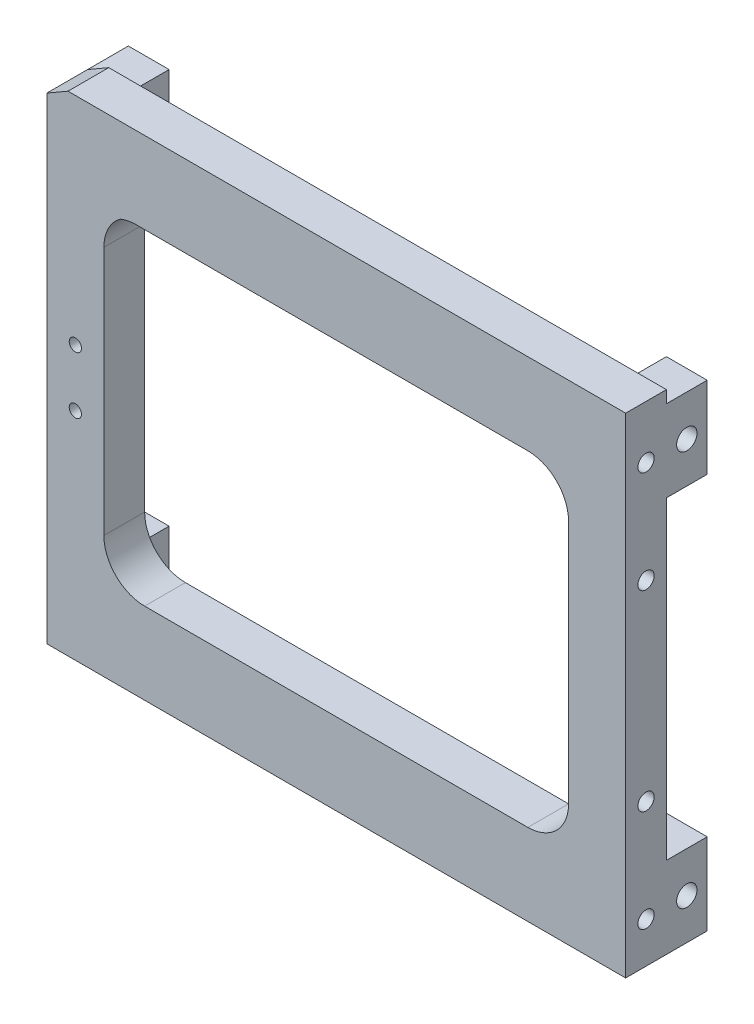
SolidWorks part; units mm, degrees
material "1060 合金"
ref_plane "前视基准面" through (0, 0, 0) normal (0, 0, 1) x (1, 0, 0)
ref_plane "上视基准面" through (0, 0, 0) normal (0, 1, 0) x (1, 0, 0)
ref_plane "右视基准面" through (0, 0, 0) normal (1, 0, 0) x (0, 0, -1)
sketch "草图1" plane through (0, 0, 0) normal (0, 0, 1) x (1, 0, 0)
  line L0 (-51.8038, 40) -> (-57, 37)
  line L1 (-65.8038, 60) -> (71, 60)
  line L2 (-71, 57) -> (-71, -60)
  line L3 (-71, -60) -> (71, -60)
  line L4 (71, 60) -> (71, -60)
  line L5 (-51.8038, 40) -> (57, 40)
  line L6 (-57, 37) -> (-57, -40)
  line L7 (-57, -40) -> (57, -40)
  line L8 (57, 40) -> (57, -40)
  line L9 (-65.8038, 60) -> (-71, 57)
  point P0 (0, -40)
  point P8 (71, 0)
  point P9 (57, 0)
  point P11 (2.5981, 60)
  point P12 (2.5981, 40)
  dimension "D1" = 142
  dimension "D2" = 117
  dimension "D3" = 20
  dimension "D4" = 14
  dimension "D5" = 60
  dimension "D6" = 14
  dimension "D7" = 3
extrude "凸台-拉伸1" add sketch "草图1" along normal mid plane 10
fillet "圆角1" radius 10 3 edges at (-57, -40, 0) (57, -40, 0) (57, 40, 0)
fillet "圆角2" radius 10 2 edges at (-51.8038, 40, 0) (-57, 37, 0)
sketch "草图2" plane through (0, 0, -5) normal (0, 0, 1) x (1, 0, 0)
  line L0 (71, -60) -> (71, 60) construction
  line L1 (-71, 57) -> (-61, 57)
  line L2 (-71, 57) -> (-71, 37)
  line L3 (-71, 37) -> (-61, 37)
  line L4 (-61, 57) -> (-61, 37)
  line L5 (-71, -60) -> (-61, -60)
  line L6 (-71, -60) -> (-71, -40)
  line L7 (-71, -40) -> (-61, -40)
  line L8 (-61, -60) -> (-61, -40)
  line L9 (71, 57) -> (61, 57)
  line L10 (71, 57) -> (71, 37)
  line L11 (71, 37) -> (61, 37)
  line L12 (61, 57) -> (61, 37)
  line L15 (71, -60) -> (61, -60)
  line L16 (71, -60) -> (71, -40)
  line L17 (71, -40) -> (61, -40)
  line L18 (61, -60) -> (61, -40)
  dimension "D1" = 20
  dimension "D2" = 20
  dimension "D3" = 10
  dimension "D4" = 10
extrude "凸台-拉伸2" add sketch "草图2" against normal blind 10
sketch "草图3" plane through (-71, 0, 0) normal (-1, 0, 0) x (0, 0, 1)
  line L0 (-15, 47) -> (5, 47) construction
  line L1 (-15, 57) -> (-15, 37) construction
  line L2 (5, 57) -> (5, -60) construction
  line L3 (-15, -50) -> (5, -50) construction
  line L4 (-15, -40) -> (-15, -60) construction
  circle A0 centre (-10, 47) radius 2.5
  circle A1 centre (0, 47) radius 2
  circle A2 centre (-10, -50) radius 2.5
  circle A3 centre (0, -50) radius 2
  circle A4 centre (0, 22) radius 2
  circle A5 centre (0, -25) radius 2
  dimension "D1" = 4
  dimension "D5" = 5
  dimension "D2" = 5
  dimension "D3" = 25
  dimension "D4" = 25
extrude "切除-拉伸1" cut sketch "草图3" against normal blind 12
sketch "草图4" plane through (71, 0, 0) normal (1, 0, 0) x (0, 0, -1)
  circle A0 centre (10, -50) radius 2.5 construction
  circle A1 centre (0, -50) radius 2 construction
  circle A2 centre (0, 47) radius 2 construction
  circle A3 centre (10, 47) radius 2.5 construction
  circle A4 centre (10, -50) radius 2.5
  circle A5 centre (0, -50) radius 2
  circle A6 centre (0, 47) radius 2
  circle A7 centre (10, 47) radius 2.5
  circle A8 centre (0, -25) radius 2 construction
  circle A9 centre (0, 22) radius 2 construction
  circle A10 centre (0, -25) radius 2
  circle A11 centre (0, 22) radius 2
extrude "切除-拉伸2" cut sketch "草图4" against normal blind 20
sketch "草图5" plane through (0, 0, 5) normal (0, 0, 1) x (1, 0, 0)
  line L0 (-71, 57) -> (-71, -60) construction
  circle A0 centre (-64, 7) radius 1.5
  circle A1 centre (-64, -7) radius 1.5
  point P7 (0, 0)
  dimension "D4" = 3
  dimension "D1" = 14
  dimension "D2" = 7
  dimension "D3" = 7
extrude "切除-拉伸3" cut sketch "草图5" against normal through all
